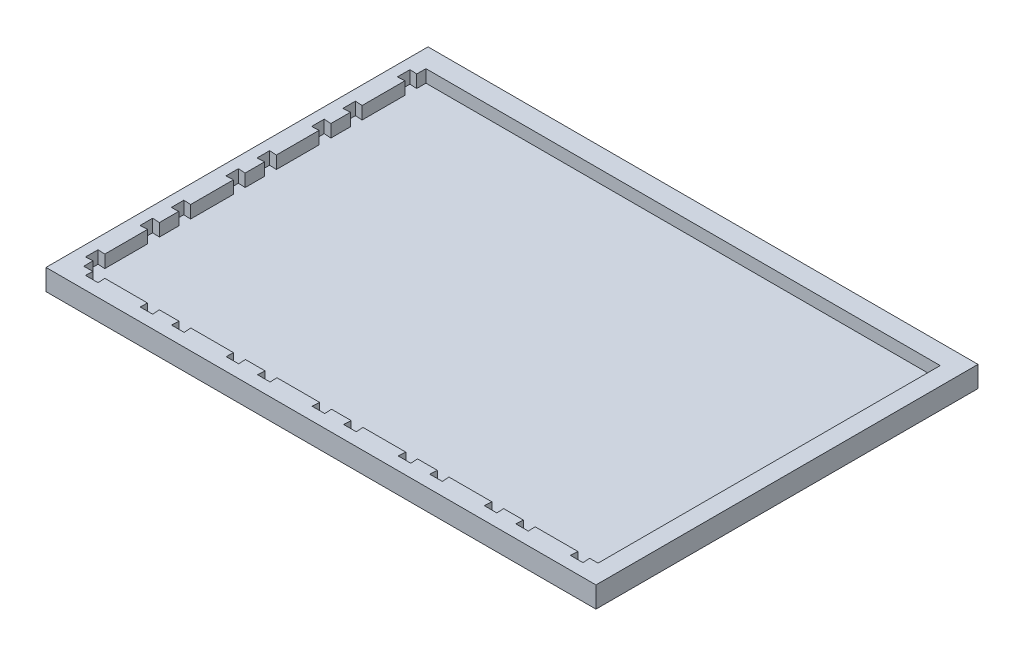
SolidWorks part; units mm, degrees
ref_plane "Front Plane" through (0, 0, 0) normal (0, 0, 1) x (1, 0, 0)
ref_plane "Top Plane" through (0, 0, 0) normal (0, 1, 0) x (1, 0, 0)
ref_plane "Right Plane" through (0, 0, 0) normal (1, 0, 0) x (0, 0, -1)
sketch "Sketch1" plane through (0, 0, 0) normal (0, 1, 0) x (1, 0, 0)
  line L1 (-65.5, -45.5) -> (65.5, -45.5)
  line L2 (-65.5, -45.5) -> (-65.5, 45.5)
  line L3 (-65.5, 45.5) -> (65.5, 45.5)
  line L4 (65.5, -45.5) -> (65.5, 45.5)
  line L5 (-65.5, -45.5) -> (65.5, 45.5) construction
  line L6 (-65.5, 45.5) -> (65.5, -45.5) construction
  point P0 (0, 0)
  dimension "D1" = 91
  dimension "D2" = 131
extrude "Boss-Extrude1" add sketch "Sketch1" along normal blind 5
sketch "Sketch3" plane through (0, 5, 0) normal (0, 1, 0) x (1, 0, 0)
  line L1 (-61.25, -40.75) -> (-59.05, -40.75)
  line L2 (-61.25, -40.75) -> (-61.25, -38.55)
  line L5 (-61.25, -40.75) -> (61.25, 40.75) construction
  line L6 (-61.25, 40.75) -> (61.25, -40.75) construction
  line L13 (0, -40.75) -> (0, 40.75) construction
  line L15 (-59.05, -40.75) -> (-59.15, -42.45)
  line L16 (-59.15, -42.45) -> (-56.15, -42.45)
  line L17 (-56.15, -42.45) -> (-56.25, -40.75)
  line L19 (-46.05, -40.75) -> (-46.15, -42.45)
  line L20 (-46.15, -42.45) -> (-43.15, -42.45)
  line L21 (-43.15, -42.45) -> (-43.25, -40.75)
  line L70 (-38.55, -40.75) -> (-38.65, -42.45)
  line L71 (-38.65, -42.45) -> (-35.65, -42.45)
  line L72 (-35.65, -42.45) -> (-35.75, -40.75)
  line L73 (-25.55, -40.75) -> (-25.65, -42.45)
  line L74 (-25.65, -42.45) -> (-22.65, -42.45)
  line L75 (-22.65, -42.45) -> (-22.75, -40.75)
  line L76 (-18.05, -40.75) -> (-18.15, -42.45)
  line L77 (-18.15, -42.45) -> (-15.15, -42.45)
  line L78 (-15.15, -42.45) -> (-15.25, -40.75)
  line L79 (-5.05, -40.75) -> (-5.15, -42.45)
  line L80 (-5.15, -42.45) -> (-2.15, -42.45)
  line L81 (-2.15, -42.45) -> (-2.25, -40.75)
  line L82 (2.45, -40.75) -> (2.35, -42.45)
  line L83 (2.35, -42.45) -> (5.35, -42.45)
  line L84 (5.35, -42.45) -> (5.25, -40.75)
  line L85 (15.45, -40.75) -> (15.35, -42.45)
  line L86 (15.35, -42.45) -> (18.35, -42.45)
  line L87 (18.35, -42.45) -> (18.25, -40.75)
  line L88 (22.95, -40.75) -> (22.85, -42.45)
  line L89 (22.85, -42.45) -> (25.85, -42.45)
  line L90 (25.85, -42.45) -> (25.75, -40.75)
  line L91 (35.95, -40.75) -> (35.85, -42.45)
  line L92 (35.85, -42.45) -> (38.85, -42.45)
  line L93 (38.85, -42.45) -> (38.75, -40.75)
  line L94 (43.45, -40.75) -> (43.35, -42.45)
  line L95 (43.35, -42.45) -> (46.35, -42.45)
  line L96 (46.35, -42.45) -> (46.25, -40.75)
  line L97 (56.45, -40.75) -> (56.35, -42.45)
  line L98 (56.35, -42.45) -> (59.35, -42.45)
  line L99 (59.35, -42.45) -> (59.25, -40.75)
  line L100 (-56.25, -40.75) -> (-46.05, -40.75)
  line L101 (-43.25, -40.75) -> (-38.55, -40.75)
  line L102 (-35.75, -40.75) -> (-25.55, -40.75)
  line L103 (-22.75, -40.75) -> (-18.05, -40.75)
  line L104 (-15.25, -40.75) -> (-5.05, -40.75)
  line L105 (-2.25, -40.75) -> (2.45, -40.75)
  line L106 (5.25, -40.75) -> (15.45, -40.75)
  line L107 (18.25, -40.75) -> (22.95, -40.75)
  line L108 (25.75, -40.75) -> (35.95, -40.75)
  line L109 (38.75, -40.75) -> (43.45, -40.75)
  line L110 (46.25, -40.75) -> (56.45, -40.75)
  line L111 (59.25, -40.75) -> (61.25, -40.75)
  line L112 (-61.25, 38.55) -> (-62.95, 38.65)
  line L113 (-62.95, 38.65) -> (-62.95, 35.65)
  line L115 (-62.95, 35.65) -> (-61.25, 35.75)
  line L116 (-61.25, 25.55) -> (-62.95, 25.65)
  line L117 (-62.95, 25.65) -> (-62.95, 22.65)
  line L118 (-62.95, 22.65) -> (-61.25, 22.75)
  line L119 (-61.25, 18.1167) -> (-62.95, 18.2167)
  line L120 (-62.95, 18.2167) -> (-62.95, 15.2167)
  line L121 (-62.95, 15.2167) -> (-61.25, 15.3167)
  line L122 (-61.25, 5.1167) -> (-62.95, 5.2167)
  line L123 (-62.95, 5.2167) -> (-62.95, 2.2167)
  line L124 (-62.95, 2.2167) -> (-61.25, 2.3167)
  line L125 (-61.25, -2.3167) -> (-62.95, -2.2167)
  line L126 (-62.95, -2.2167) -> (-62.95, -5.2167)
  line L127 (-62.95, -5.2167) -> (-61.25, -5.1167)
  line L128 (-61.25, -15.3167) -> (-62.95, -15.2167)
  line L129 (-62.95, -15.2167) -> (-62.95, -18.2167)
  line L130 (-62.95, -18.2167) -> (-61.25, -18.1167)
  line L131 (-61.25, -22.75) -> (-62.95, -22.65)
  line L132 (-62.95, -22.65) -> (-62.95, -25.65)
  line L133 (-62.95, -25.65) -> (-61.25, -25.55)
  line L134 (-61.25, -35.75) -> (-62.95, -35.65)
  line L135 (-62.95, -35.65) -> (-62.95, -38.65)
  line L136 (-62.95, -38.65) -> (-61.25, -38.55)
  line L137 (-61.25, 38.55) -> (-61.25, 40.75)
  line L138 (-61.25, 25.55) -> (-61.25, 35.75)
  line L139 (-61.25, 5.1167) -> (-61.25, 15.3167)
  line L140 (-61.25, -2.3167) -> (-61.25, 2.3167)
  line L141 (-61.25, -15.3167) -> (-61.25, -5.1167)
  line L142 (-61.25, -22.75) -> (-61.25, -18.1167)
  line L143 (-61.25, -35.75) -> (-61.25, -25.55)
  line L144 (-61.25, 18.1167) -> (-61.25, 22.75)
  line L177 (-61.25, 40.75) -> (61.25, 40.75)
  line L178 (61.25, -40.75) -> (61.25, 40.75)
  point P0 (0, 0)
  dimension "D2" = 122.5
  dimension "D3" = 3
  dimension "D4" = 2.2
  dimension "D5" = 0.1
  dimension "D6" = 1.7
  dimension "D7" = 0.1
  dimension "D8" = 10
  dimension "D10" = 4.5
  dimension "D11" = 81.5
  dimension "D15" = 4
  dimension "D17" = 6
extrude "Cut-Extrude2" cut sketch "Sketch3" against normal blind 3 contours L111 L178 L177 L137 L112 L113 L115 L138 L116 L117 L118 L144 L119 L120 L121 L139 L122 L123 L124 L140 L125 L126 L127 L141 L128 L129 L130 L142 L131 L132 L133 L143 L134 L135 L136 L2 L1 L15 L16 L17 L100 L19 L20 L21 L101 L70 L71 L72 L102 L73 L74 | L178 L177 L137 L112 L113 L115 L138 L116 L117 L118 L144 L119 L120 L121 L139 L122 L123 L124 L140 L125 L126 L127 L141 L128 L129 L130 L142 L131 L132 L133 L143 L134 L135 L136 L2 L1 L15 L16 L17 L100 L19 L20 L21 L101 L70 L71 L72 L102 L73 L74 L75 L103 L76 L77 L78 L104 L79 L80 L81 L105 L82 L83 L84 L106 L85 L86 L87 L107 L88 L89 L90 L108 L91 L92 L93 L109 L94 L95 L96 L110 L97 L98 L99 L111 region at (-0.2424, 5, 0.2442)
